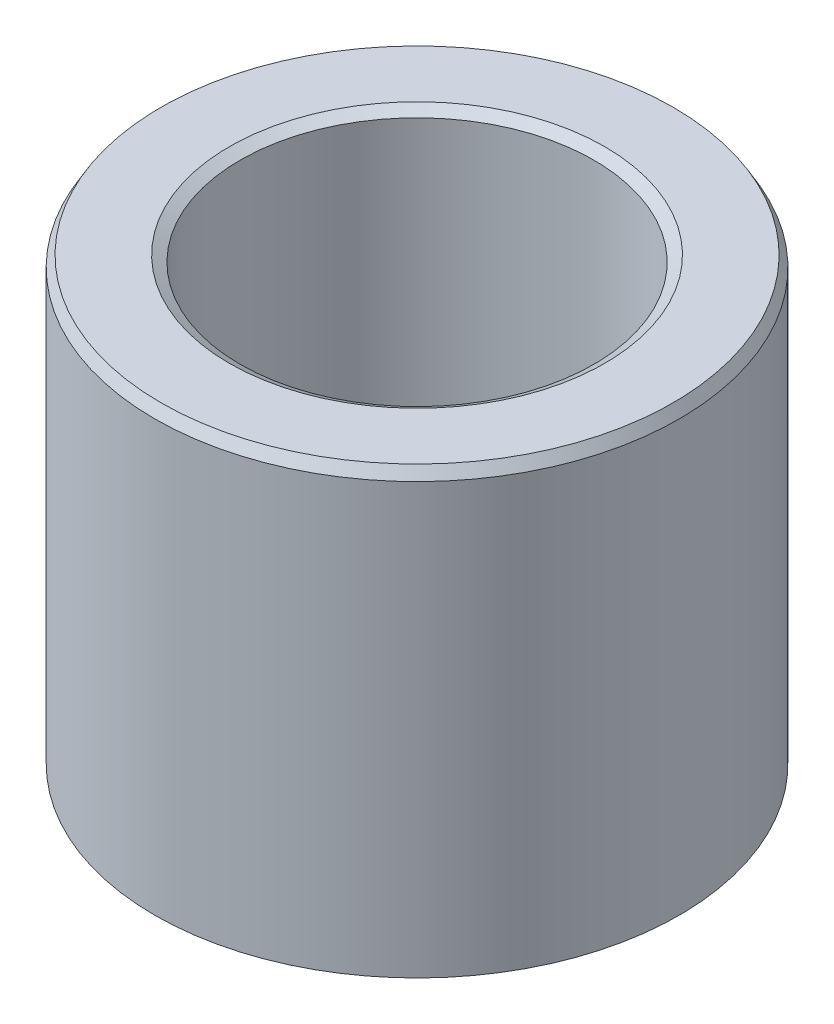
SolidWorks part; units mm, degrees
ref_plane "Front Plane" through (0, 0, 0) normal (0, 0, 1) x (1, 0, 0)
ref_plane "Top Plane" through (0, 0, 0) normal (0, 1, 0) x (1, 0, 0)
ref_plane "Right Plane" through (0, 0, 0) normal (1, 0, 0) x (0, 0, -1)
sketch "Sketch1" plane through (0, 0, 0) normal (0, 1, 0) x (1, 0, 0)
  circle A0 centre (0, 0) radius 47.5
  dimension "SLEEVE_OD" = 95
extrude "Boss-Extrude1" add sketch "Sketch1" along normal blind 80.9451
sketch "Sketch2" plane through (0, 0, 0) normal (0, 1, 0) x (1, 0, 0)
  circle A0 centre (0, 0) radius 32.0364
  dimension "BORE_D" = 64.0728
extrude "Cut-Extrude1" cut sketch "Sketch2" along normal through all
chamfer "Chamfer1" distance 1.9582 angle 30 4 edges at (0, 80.9451, 32.0364) (0, 0, 32.0364) (0, 0, 47.5) (0, 80.9451, 47.5) first distance on face at (0, 80.9451, 32.0364) first distance on face at (0, 0, 32.0364) first distance on face at (0, 80.9451, 47.5)
